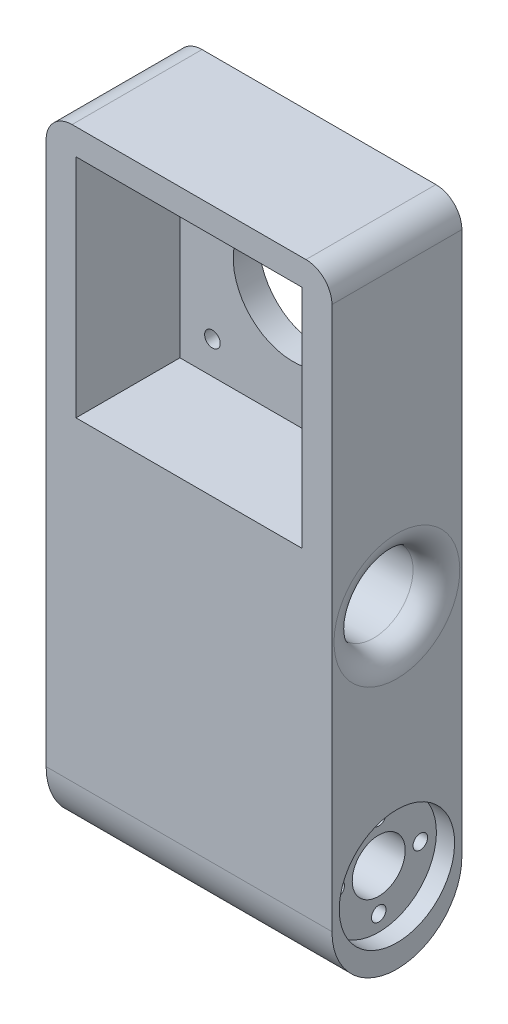
SolidWorks part; units mm, degrees
ref_plane "Front" through (0, 0, 0) normal (0, 0, 1) x (1, 0, 0)
ref_plane "Top" through (0, 0, 0) normal (0, 1, 0) x (1, 0, 0)
ref_plane "Right" through (0, 0, 0) normal (1, 0, 0) x (0, 0, -1)
sketch "Sketch1" plane through (0, 0, 0) normal (0, 0, 1) x (1, 0, 0)
  line L1 (-27.5, 61) -> (27.5, 61)
  line L2 (-27.5, 61) -> (-27.5, -61)
  line L3 (-27.5, -61) -> (27.5, -61)
  line L4 (27.5, 61) -> (27.5, -61)
  line L5 (-27.5, 61) -> (27.5, -61) construction
  line L6 (-27.5, -61) -> (27.5, 61) construction
  line L7 (-15.5, 49.75) -> (15.5, 49.75) construction
  line L8 (-15.5, 49.75) -> (-15.5, 18.75) construction
  line L9 (-15.5, 18.75) -> (15.5, 18.75) construction
  line L10 (15.5, 49.75) -> (15.5, 18.75) construction
  line L11 (-15.5, 49.75) -> (15.5, 18.75) construction
  line L12 (-15.5, 18.75) -> (15.5, 49.75) construction
  circle A0 centre (0, 34.25) radius 11.5
  circle A1 centre (-15.5, 49.75) radius 1.5
  circle A2 centre (15.5, 49.75) radius 1.5
  circle A3 centre (-15.5, 18.75) radius 1.5
  circle A4 centre (15.5, 18.75) radius 1.5
  point P0 (0, 0)
  point P8 (0, -61)
  dimension "D3" = 23
  dimension "D1" = 55
  dimension "D2" = 122
  dimension "D4" = 26.75
  dimension "D5" = 31
  dimension "D6" = 31
extrude "Boss-Extrude1" add sketch "Sketch1" along normal blind 25
sketch "Sketch2" plane through (0, 0, 25) normal (0, 0, 1) x (1, 0, 0)
  line L1 (-21.75, 56) -> (21.75, 56)
  line L2 (-21.75, 56) -> (-21.75, 12.5)
  line L3 (-21.75, 12.5) -> (21.75, 12.5)
  line L4 (21.75, 56) -> (21.75, 12.5)
  line L5 (-21.75, 56) -> (21.75, 12.5) construction
  line L6 (-21.75, 12.5) -> (21.75, 56) construction
  point P0 (0, 34.25)
  dimension "D1" = 43.5
  dimension "D2" = 43.5
extrude "Cut-Extrude1" cut sketch "Sketch2" against normal blind 20
sketch "Sketch3" plane through (27.5, 0, 0) normal (1, 0, 0) x (0, 0, -1)
  line L0 (-25, 61) -> (0, 61) construction
  circle A0 centre (-12.5, -0.5) radius 7.6
  circle A1 centre (-12.5, -45.5) radius 5.1
  dimension "D1" = 61.5
  dimension "D2" = 45
  dimension "D3" = 15.2
  dimension "D4" = 10.2
extrude "Cut-Extrude2" cut sketch "Sketch3" against normal through all
sketch "Sketch4" plane through (27.5, 0, 0) normal (1, 0, 0) x (0, 0, -1)
  circle A0 centre (-12.5, -45.5) radius 11.1
  dimension "D1" = 22.2
extrude "Cut-Extrude3" cut sketch "Sketch4" against normal blind 3.5
sketch "Sketch5" plane through (24, 0, 0) normal (1, 0, 0) x (0, 0, -1)
  circle A0 centre (-12.5, -37.5) radius 1.4
  circle A1 centre (-12.5, -45.5) radius 5.1 construction
  circle A5 centre (-12.5, -45.5) radius 5.5 construction
  circle A6 centre (-4.5, -45.5) radius 1.4
  circle A7 centre (-12.5, -53.5) radius 1.4
  circle A8 centre (-20.5, -45.5) radius 1.4
  dimension "D1" = 8
  dimension "D3" = 2.8
  dimension "D2" = 4
extrude "Cut-Extrude4" cut sketch "Sketch5" against normal blind 10
sketch "Sketch6" plane through (0, 0, 0) normal (0, 0, -1) x (-1, 0, 0)
  line L0 (27.5, -61) -> (-27.5, -61) construction
  circle A0 centre (0, -23) radius 4.1
  dimension "D1" = 38
  dimension "D2" = 8.2
extrude "Cut-Extrude5" cut sketch "Sketch6" against normal blind 18
fillet "Fillet1" radius 5 2 edges at (27.5, 61, 12.5) (-27.5, 61, 12.5)
fillet "Fillet2" radius 4.5 2 edges at (-27.5, 7.1, 12.5) (27.5, 7.1, 12.5)
fillet "Fillet3" 2 edges at (0, -61, 25) (0, -61, 0) type full round first side face at (0, 34.25, 25) second side face at (-4.1, -23, 0) middle face at (0, -61, 12.5)
sketch "Sketch7" plane through (0, 0, 0) normal (0, 0, -1) x (-1, 0, 0)
  circle A0 centre (-15.5, 49.75) radius 3.5
  circle A1 centre (0, 34.25) radius 11.5 construction
  circle A2 centre (15.5, 49.75) radius 3.5
  circle A3 centre (15.5, 18.75) radius 3.5
  circle A4 centre (-15.5, 18.75) radius 3.5
  dimension "D1" = 4
  dimension "D2" = 7
extrude "Cut-Extrude6" cut sketch "Sketch7" against normal blind 2
